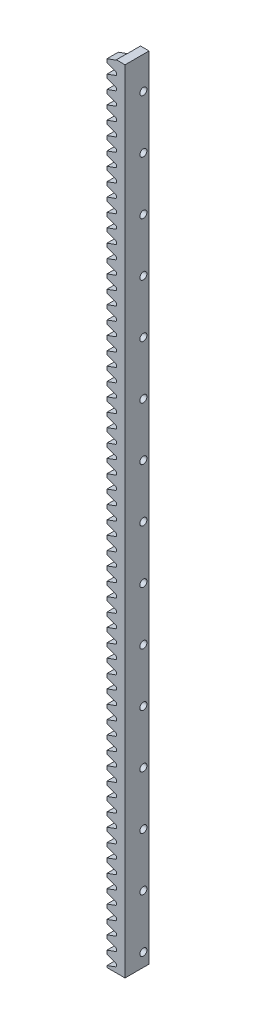
SolidWorks part; units mm, degrees
material "6061-T6 (SS)"
ref_plane "前视基准面" through (0, 0, 0) normal (0, 0, 1) x (1, 0, 0)
ref_plane "上视基准面" through (0, 0, 0) normal (0, 1, 0) x (1, 0, 0)
ref_plane "右视基准面" through (0, 0, 0) normal (1, 0, 0) x (0, 0, -1)
ref_axis "基准轴1" through (0, -55, 0) along (0, 1, 0)
sketch "SketchCI.m_strSketchName" plane through (0, 0, 0) normal (0, 0, 1) x (1, 0, 0)
  line L0 (-1.5, 2.3562) -> (-1.5, -327.511)
  line L1 (-1.5, -327.511) -> (19.05, -327.511)
  line L2 (19.05, -327.511) -> (19.05, 2.3562)
  line L3 (19.05, 2.3562) -> (-1.5, 2.3562)
extrude "拉伸CI" add sketch "SketchCI.m_strSketchName" along normal blind 4
sketch "齿草图大直齿轮" plane through (0, 0, 0) normal (0, 0, 1) x (1, 0, 0)
  line L0 (-1.5, 1.7241) -> (-1.5, -1.7241)
  line L1 (-1.5, -1.7241) -> (1.5789, -0.6034)
  line L2 (1.875, -0.1806) -> (1.875, 0.1806)
  line L3 (1.5789, 0.6034) -> (-1.5, 1.7241)
  arc A0 (1.5789, -0.6034) -> (1.875, -0.1806) centre (1.425, -0.1806) ccw
  arc A1 (1.875, 0.1806) -> (1.5789, 0.6034) centre (1.425, 0.1806) ccw
  dimension "D1" = 0.9
  dimension "D2" = 0.9
  dimension "FLANKONEANGLE" = 70
  dimension "FLANKTWOANGLE" = 70
extrude "齿拉伸切除大直齿轮" cut sketch "齿草图大直齿轮" against normal blind 9.525 and the other way blind 9.525
pattern_linear "齿形大直齿轮" count 70 spacing 4.7124 along (0, -1, 0) of "齿拉伸切除大直齿轮"
sketch "辅助草图大直齿轮" plane through (0, 0, 0) normal (0, 0, 1) x (1, 0, 0)
  line L0 (0, 0) -> (0, -329.8672) construction
sketch "草图1" plane through (0, 0, 4) normal (0, 0, 1) x (1, 0, 0)
  line L0 (-1.5, -327.511) -> (19.05, -327.511) construction
  line L1 (19.05, 2.3562) -> (4.9, 2.3562)
  line L2 (19.05, 2.3562) -> (19.05, -327.511)
  line L3 (19.05, -327.511) -> (4.9, -327.511)
  line L4 (4.9, 2.3562) -> (4.9, -327.511)
  line L6 (-1.5, -15.8612) -> (-1.5, -17.1255) construction
  dimension "D1" = 6.4
extrude "切除-拉伸1" cut sketch "草图1" against normal through all
sketch "草图2" plane through (0, 0, 0) normal (0, 0, -1) x (-1, 0, 0)
  line L0 (-1.875, 0.1806) -> (-1.875, -0.1806) construction
  line L1 (-4.9, -327.511) -> (-1.875, -327.511)
  line L2 (-4.9, -327.511) -> (-4.9, 2.3562)
  line L3 (-4.9, 2.3562) -> (-1.875, 2.3562)
  line L4 (-1.875, -327.511) -> (-1.875, 2.3562)
  line L5 (-4.9, 2.3562) -> (1.5, 2.3562) construction
extrude "凸台-拉伸1" add sketch "草图2" along normal blind 4.5
sketch "草图3" plane through (1.875, 0, 0) normal (-1, 0, 0) x (0, 0, 1)
  line L0 (-2.5, -327.511) -> (-2.5, 21.2057) construction
  line L1 (-4.5, -327.511) -> (0, -327.511) construction
  line L2 (0, -327.511) -> (0, -325.3354) construction
  line L3 (0, -322.7986) -> (-2.5, -322.7986) construction
  line L4 (0, -324.9743) -> (0, -320.623) construction
  line L5 (0, -303.9491) -> (-7.1234, -303.9491) construction
  line L10 (0, -306.1247) -> (0, -301.7735) construction
  line L15 (0, -287.2752) -> (0, -282.9239) construction
  line L16 (0, -285.0995) -> (-7.1234, -285.0995) construction
  line L19 (0, -268.4256) -> (0, -264.0743) construction
  line L21 (0, -266.25) -> (-6.4462, -266.25) construction
  line L24 (0, -249.5761) -> (0, -245.2248) construction
  line L25 (0, -247.4004) -> (-6.4462, -247.4004) construction
  line L28 (0, -230.7265) -> (0, -226.3752) construction
  line L30 (0, -228.5509) -> (-6.4462, -228.5509) construction
  line L33 (0, -211.8769) -> (0, -207.5257) construction
  line L34 (0, -209.7013) -> (-6.4462, -209.7013) construction
  line L37 (0, -193.0274) -> (0, -188.6761) construction
  line L39 (0, -190.8518) -> (-6.4462, -190.8518) construction
  line L42 (0, -174.1778) -> (0, -169.8266) construction
  line L43 (0, -172.0022) -> (-7.1234, -172.0022) construction
  line L45 (0, -155.3283) -> (0, -150.977) construction
  line L46 (0, -153.1526) -> (-7.1234, -153.1526) construction
  line L48 (0, -136.4787) -> (0, -132.1275) construction
  line L49 (0, -134.3031) -> (-7.1234, -134.3031) construction
  line L51 (0, -117.6292) -> (0, -113.2779) construction
  line L52 (0, -115.4535) -> (-7.1234, -115.4535) construction
  line L54 (0, -98.7796) -> (0, -94.4283) construction
  line L55 (0, -96.604) -> (-8.3313, -96.604) construction
  line L57 (0, -79.9301) -> (0, -75.5788) construction
  line L58 (0, -77.7544) -> (-7.1234, -77.7544) construction
  line L60 (0, -61.0805) -> (0, -56.7292) construction
  line L61 (0, -58.9049) -> (-7.1234, -58.9049) construction
  line L63 (0, -42.2309) -> (0, -37.8797) construction
  line L64 (0, -40.0553) -> (-7.1234, -40.0553) construction
  line L66 (0, -23.3814) -> (0, -19.0301) construction
  line L67 (0, -21.2058) -> (-7.1234, -21.2058) construction
  line L69 (0, -4.5318) -> (0, -0.1806) construction
  line L70 (0, -2.3562) -> (-7.1234, -2.3562) construction
  circle A0 centre (-2.5, -322.7986) radius 1.25
  circle A1 centre (-2.5, -303.9491) radius 1.25
  circle A2 centre (-2.5, -285.0995) radius 1.25
  circle A3 centre (-2.5, -266.25) radius 1.25
  circle A4 centre (-2.5, -247.4004) radius 1.25
  circle A5 centre (-2.5, -228.5509) radius 1.25
  circle A6 centre (-2.5, -209.7013) radius 1.25
  circle A7 centre (-2.5, -190.8518) radius 1.25
  circle A8 centre (-2.5, -172.0022) radius 1.25
  circle A9 centre (-2.5, -153.1526) radius 1.25
  circle A10 centre (-2.5, -134.3031) radius 1.25
  circle A11 centre (-2.5, -115.4535) radius 1.25
  circle A12 centre (-2.5, -96.604) radius 1.25
  circle A13 centre (-2.5, -77.7544) radius 1.25
  circle A14 centre (-2.5, -58.9049) radius 1.25
  circle A15 centre (-2.5, -40.0553) radius 1.25
  circle A16 centre (-2.5, -21.2058) radius 1.25
  circle A17 centre (-2.5, -2.3562) radius 1.25
  dimension "D2" = 2.5
  dimension "D1" = 2.5
extrude "切除-拉伸2" cut sketch "草图3" against normal up to next
sketch "草图4" plane through (4.9, 0, 0) normal (1, 0, 0) x (0, 0, -1)
  line L0 (4.5, 2.3562) -> (4.5, -327.511) construction
  line L1 (-4, 2.3562) -> (4.5, 2.3562)
  line L2 (-4, 2.3562) -> (-4, -47.511)
  line L3 (-4, -47.511) -> (4.5, -47.511)
  line L4 (4.5, 2.3562) -> (4.5, -47.511)
  line L5 (4.5, -327.511) -> (-4, -327.511) construction
  dimension "D1" = 280
extrude "切除-拉伸3" cut sketch "草图4" against normal through all
sketch "草图5" plane through (0, 0, 0) normal (0, 0, -1) x (-1, 0, 0)
  line L1 (-1.875, -331.511) -> (5.5, -331.511)
  line L2 (-1.875, -331.511) -> (-1.875, -43.511)
  line L3 (-1.875, -43.511) -> (5.5, -43.511)
  line L4 (5.5, -331.511) -> (5.5, -43.511)
  line L5 (-1.875, -327.511) -> (-1.875, -325.3354) construction
  line L6 (1.5, -327.511) -> (-1.875, -327.511) construction
  line L7 (1.5, -326.8789) -> (1.5, -327.511) construction
  line L8 (-1.875, -47.511) -> (-4.9, -47.511) construction
  dimension "D1" = 4
  dimension "D2" = 4
  dimension "D3" = 4
extrude "凸台-拉伸2" [suppressed] add sketch "草图5" along normal blind 1
